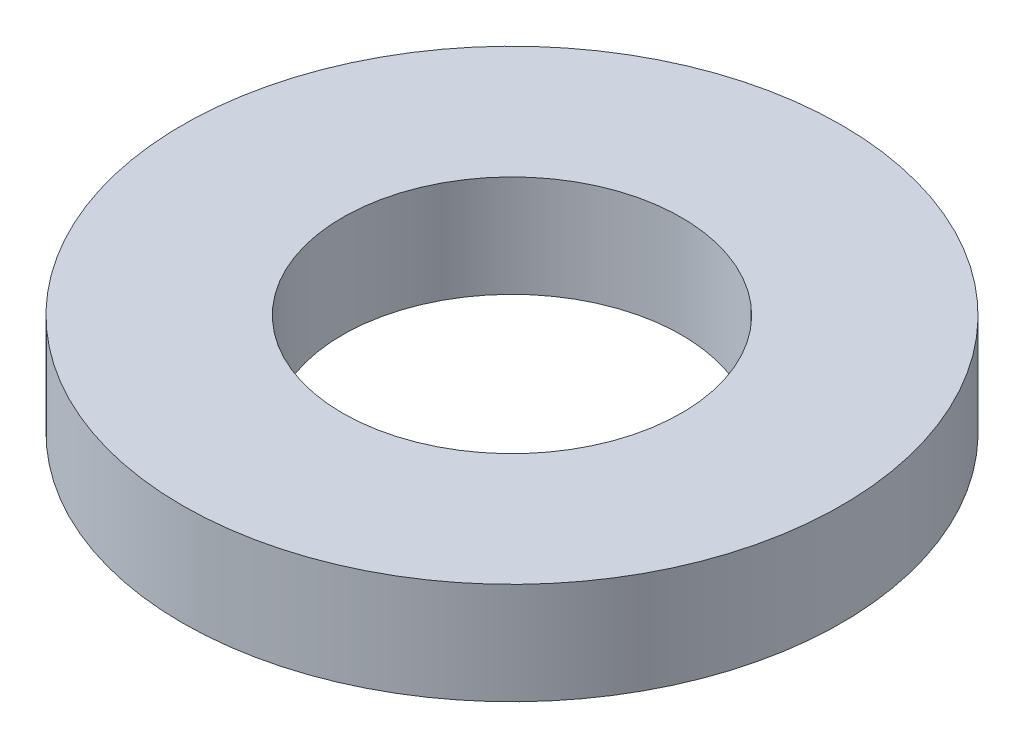
SolidWorks part; units mm, degrees
ref_plane "Front Plane" through (0, 0, 0) normal (0, 0, 1) x (1, 0, 0)
ref_plane "Top Plane" through (0, 0, 0) normal (0, 1, 0) x (1, 0, 0)
ref_plane "Right Plane" through (0, 0, 0) normal (1, 0, 0) x (0, 0, -1)
sketch "Sketch1" plane through (0, 0, 0) normal (0, 1, 0) x (1, 0, 0)
  circle A0 centre (0, 0) radius 87.5
  dimension "FLANGE_OD" = 175
extrude "Boss-Extrude1" add sketch "Sketch1" along normal blind 27
sketch "Sketch2" plane through (0, 0, 0) normal (0, 1, 0) x (1, 0, 0)
  circle A0 centre (0, 0) radius 45
  dimension "BORE_D" = 90
extrude "Cut-Extrude1" cut sketch "Sketch2" along normal through all
sketch "Sketch3" plane through (0, 27, 0) normal (0, 1, 0) x (1, 0, 0)
  circle A0 centre (0, 0) radius 36.2276 construction
  circle A1 centre (-36.2276, 0) radius 3.6377
  dimension "BOLT_D" = 7.2754
  dimension "BOLT_PCD" = 72.4552
extrude "Cut-Extrude2" cut sketch "Sketch3" against normal blind 26.0423 rebuild error yes
pattern_circular "CirPattern1" count 6 over 360 rebuild error yes
